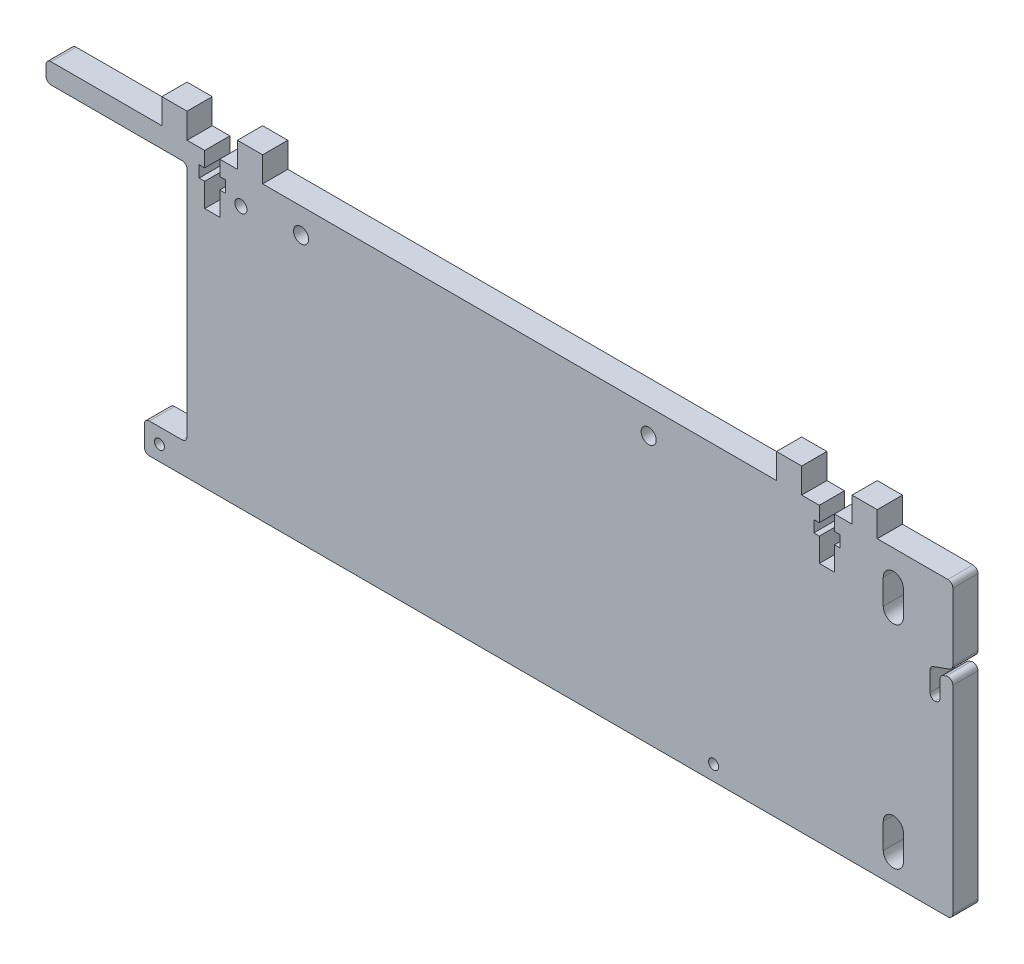
SolidWorks part; units mm, degrees
ref_plane "Plan de face" through (0, 0, 0) normal (0, 0, 1) x (1, 0, 0)
ref_plane "Plan de dessus" through (0, 0, 0) normal (0, 1, 0) x (1, 0, 0)
ref_plane "Plan de droite" through (0, 0, 0) normal (1, 0, 0) x (0, 0, -1)
sketch "Esquisse1" plane through (0, 0, 0) normal (0, 0, 1) x (1, 0, 0)
  line L0 (-90, 0) -> (90, 0) construction
  line L1 (90, 0) -> (90, -58) construction
  line L2 (90, -58) -> (-90, -58) construction
  line L3 (-90, -58) -> (-90, 0) construction
  line L4 (0, 0) -> (0, -58) construction
  line L5 (-67, 0) -> (-90, 0)
  line L6 (-90, 0) -> (-90, -58) construction
  line L7 (90, -58) -> (-62, -58)
  line L8 (90, -58) -> (90, 0)
  line L9 (90, 0) -> (75, 0)
  line L10 (55, 0) -> (-47, 0)
  line L11 (-58.1183, 0) -> (-58.1183, -6) construction
  line L12 (75, 0) -> (75, -6) construction
  line L13 (75, -6) -> (-58.1183, -6) construction
  line L14 (-62, -4) -> (-62, -52)
  line L15 (-51.3092, -6) -> (78.1908, -6) construction
  line L16 (-39.3683, 0) -> (-39.3683, -5) construction
  line L17 (-62, -52) -> (-70.4817, -52)
  line L18 (29.6317, -5) -> (-39.3683, -5) construction
  line L19 (-70.4817, -52) -> (-70.4817, -58)
  line L20 (-62, -58) -> (-62, -4) construction
  line L21 (-62, -4) -> (-90, -4)
  line L22 (-90, -4) -> (-90, 0)
  line L23 (-70.4817, -58) -> (-62, -58)
  circle A2 centre (-39.3683, -5) radius 1.5
  circle A3 centre (29.6317, -5) radius 1.5
  circle A4 centre (-51.3092, -6) radius 1.2
  circle A5 centre (78.1908, -6) radius 1.2
  circle A6 centre (42.5183, -55) radius 1
  circle A8 centre (-67.4817, -55) radius 1
  arc A11 (-66.2317, -55) -> (-68.7317, -55) centre (-67.4817, -55) ccw construction
  arc A13 (41.2683, -55) -> (43.7683, -55) centre (42.5183, -55) ccw construction
  point P30 (0, 0)
  point P42 (-67.4817, -55)
  point P44 (-62, -56.7015)
  line B0 (67.6, -3) -> (67.6, -5.3)
  line B1 (63.5, -5.3) -> (63.5, -10)
  line B2 (66.5, -10) -> (66.5, -5.3)
  line B3 (67.6, -5.3) -> (66.5, -5.3)
  line B4 (65, 0) -> (65, -11.2208) construction
  line B5 (66.5, 0) -> (70, 0)
  line B6 (70, 5) -> (75, 5)
  line B7 (75, 5) -> (75, 0)
  line B8 (70, 5) -> (70, 0)
  line B9 (63.5, 0) -> (60, 0)
  line B10 (60, 0) -> (60, 5)
  line B11 (60, 5) -> (55, 5)
  line B12 (55, 5) -> (55, 0)
  line B13 (66.5, 0) -> (63.5, 0) construction
  line B14 (63.5, 0) -> (63.5, -3)
  line B15 (63.5, -5.3) -> (62.4, -5.3)
  line B16 (62.4, -3) -> (63.5, -3)
  line B17 (63.5, -10) -> (66.5, -10)
  line B18 (66.5, -3) -> (67.6, -3)
  line B19 (62.4, -5.3) -> (62.4, -3)
  line B20 (66.5, -3) -> (66.5, 0)
  line B21 (65, -10) -> (65, 0) construction
  line B22 (-59.6, -3) -> (-59.6, -5.3)
  line B23 (-55.5, -5.3) -> (-55.5, -10)
  line B24 (-58.5, -10) -> (-58.5, -5.3)
  line B25 (-59.6, -5.3) -> (-58.5, -5.3)
  line B26 (-57, 0) -> (-57, -11.2208) construction
  line B27 (-58.5, 0) -> (-62, 0)
  line B28 (-62, 5) -> (-67, 5)
  line B29 (-67, 5) -> (-67, 0)
  line B30 (-62, 5) -> (-62, 0)
  line B31 (-55.5, 0) -> (-52, 0)
  line B32 (-52, 0) -> (-52, 5)
  line B33 (-52, 5) -> (-47, 5)
  line B34 (-47, 5) -> (-47, 0)
  line B35 (-58.5, 0) -> (-55.5, 0) construction
  line B36 (-55.5, 0) -> (-55.5, -3)
  line B37 (-55.5, -5.3) -> (-54.4, -5.3)
  line B38 (-54.4, -3) -> (-55.5, -3)
  line B39 (-55.5, -10) -> (-58.5, -10)
  line B40 (-58.5, -3) -> (-59.6, -3)
  line B41 (-54.4, -5.3) -> (-54.4, -3)
  line B42 (-58.5, -3) -> (-58.5, 0)
  line B43 (-57, -10) -> (-57, 0) construction
  dimension "D5" = 2.4
  dimension "D8" = 3
  dimension "D11" = 6
  dimension "D16" = 122
  dimension "D17" = 2
  dimension "D2" = 58
  dimension "D3" = 180
  dimension "D4" = 129.5
  dimension "D6" = 18.75
  dimension "D7" = 5
  dimension "D9" = 69
  dimension "D10" = 6
  dimension "D12" = 4
  dimension "D13" = 25
  dimension "D14" = 51.3092
  dimension "D15" = 28
  dimension "D18" = 3
  dimension "D19" = 3
sketch_block_instance "Insert M3 plots ep 5mm-1"
sketch_block "Insert M3 plots ep 5mm" parameters "D1"=10, "D2"=5, "D3"=5
sketch_block_instance "Decoupe Insert M3-4"
sketch_block "Decoupe Insert M3" parameters "D1"=5.2, "D2"=3, "D3"=2.3, "D4"=3, "D5"=10
sketch_block_instance "Insert M3 plots ep 5mm-3"
extrude "Boss.-Extru.1" add sketch "Esquisse1" along normal blind 5 contours B40 B42 B27 B30 B28 B29 L5 L6 L8 L9 B7 B6 B8 B5 B20 B18 B0 B3 B2 B17 B1 B15 B19 B16 B14 B9 B10 B11 B12 L10 B34 B33 B32 B31 B36 B38 B41 B37 B23 B39 B24 B25 B22 region at (12.4382, -28.6909, 0)
sketch "Esquisse2" plane through (0, 0, 0) normal (0, 0, -1) x (-1, 0, 0)
  line L0 (-90, -16.277) -> (-87.46, -17.2015)
  line L1 (-87.46, -17.2015) -> (-87.46, -22.2015)
  line L2 (-87.46, -22.2015) -> (-85.46, -22.2015)
  line L3 (-85.46, -22.2015) -> (-85.46, -16.6524)
  line L4 (-85.46, -16.6524) -> (-90, -15)
  line L5 (-90, -16.277) -> (-90, -15)
  line L6 (-90, -58) -> (-90, 0) construction
  line L7 (-90, 0) -> (-75, 0) construction
  line L8 (-78.1908, -6) -> (-78.1908, -11) construction
  line L9 (-76.1908, -6) -> (-76.1908, -11)
  line L10 (-80.1908, -6) -> (-80.1908, -11)
  line L11 (-78.1908, -48) -> (-78.1908, -53) construction
  line L12 (-76.1908, -48) -> (-76.1908, -53)
  line L13 (-80.1908, -48) -> (-80.1908, -53)
  line L14 (-90, -58) -> (70.4817, -58) construction
  arc A0 (-76.1908, -6) -> (-80.1908, -6) centre (-78.1908, -6) ccw
  arc A1 (-80.1908, -11) -> (-76.1908, -11) centre (-78.1908, -11) ccw
  arc A2 (-76.1908, -48) -> (-80.1908, -48) centre (-78.1908, -48) ccw
  arc A3 (-80.1908, -53) -> (-76.1908, -53) centre (-78.1908, -53) ccw
  point P13 (-78.1908, -8.5)
  point P18 (-78.1908, -50.5)
  dimension "D1" = 1.2
  dimension "D2" = 2
  dimension "D3" = 5
  dimension "D4" = 2.54
  dimension "D5" = 15
  dimension "D6" = 110
  dimension "D7" = 5
  dimension "D8" = 5
  dimension "D9" = 4
  dimension "D10" = 5
extrude "Enlèv. mat.-Extru.1" cut sketch "Esquisse2" against normal through all
fillet "Congé1" radius 1 14 edges at (85.46, -16.6524, 2.5) (90, -15, 2.5) (90, -16.277, 2.5) (87.46, -17.2015, 2.5) (87.46, -22.2015, 2.5) (85.46, -22.2015, 2.5) (90, -58, 2.5) (90, 0, 2.5) (-90, 0, 2.5) (-90, -4, 2.5) (-62, -4, 2.5) (-62, -52, 2.5) (-70.4817, -58, 2.5) (-70.4817, -52, 2.5)
